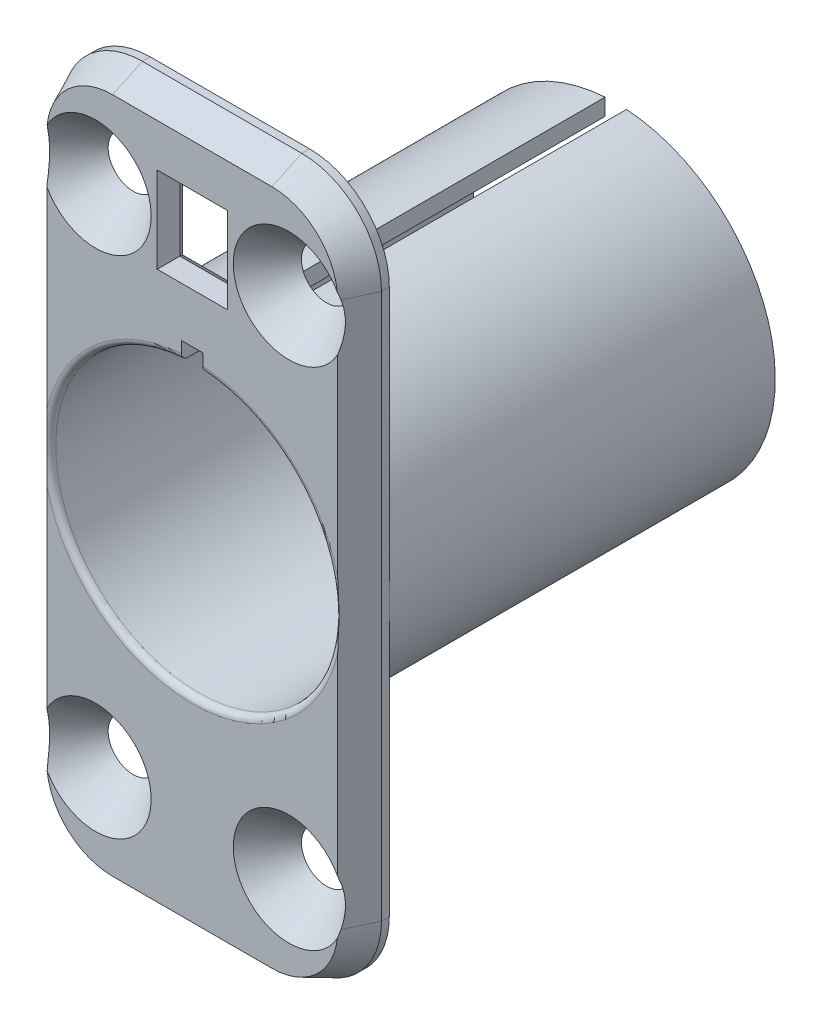
SolidWorks part; units mm, degrees
ref_plane "Front Plane" through (0, 0, 0) normal (0, 0, 1) x (1, 0, 0)
ref_plane "Top Plane" through (0, 0, 0) normal (0, 1, 0) x (1, 0, 0)
ref_plane "Right Plane" through (0, 0, 0) normal (1, 0, 0) x (0, 0, -1)
sketch "Sketch1" plane through (0, 0, 0) normal (0, 0, 1) x (1, 0, 0)
  line L1 (6.35, 28.075) -> (-6.35, 28.075)
  line L2 (12.7, 21.725) -> (12.7, -21.725)
  line L3 (6.35, -28.075) -> (-6.35, -28.075)
  line L4 (-12.7, 21.725) -> (-12.7, -21.725)
  line L5 (12.7, 28.075) -> (-12.7, -28.075) construction
  line L6 (12.7, -28.075) -> (-12.7, 28.075) construction
  arc A0 (6.35, 28.075) -> (12.7, 21.725) centre (6.35, 21.725) cw
  arc A1 (6.35, -28.075) -> (12.7, -21.725) centre (6.35, -21.725) ccw
  arc A2 (-6.35, -28.075) -> (-12.7, -21.725) centre (-6.35, -21.725) cw
  arc A3 (-12.7, 21.725) -> (-6.35, 28.075) centre (-6.35, 21.725) cw
  point P0 (0, 0)
  dimension "D3" = 6.35
  dimension "D1" = 25.4
  dimension "D2" = 56.15
extrude "Boss-Extrude1" add sketch "Sketch1" along normal blind 3
sketch "Sketch2" plane through (0, 0, 0) normal (0, 0, -1) x (-1, 0, 0)
  line L2 (-12.7, -21.725) -> (-12.7, 21.725) construction
  line L3 (12.7, 21.725) -> (12.7, -21.725) construction
  line L4 (-6.35, 28.075) -> (6.35, 28.075) construction
  line L5 (6.35, -28.075) -> (-6.35, -28.075) construction
  circle A1 centre (-7.7, -20.125) radius 2
  circle A2 centre (-7.7, 20.125) radius 2
  circle A3 centre (7.7, 20.125) radius 2
  circle A5 centre (7.7, -20.125) radius 2
  dimension "D1" = 5
  dimension "D2" = 4
  dimension "D5" = 4
  dimension "D6" = 4
  dimension "D7" = 7.95
  dimension "D8" = 7.95
  dimension "D9" = 5
  dimension "D10" = 4
  dimension "D12" = 5
  dimension "D13" = 7.95
  dimension "D3" = 7.95
  dimension "D4" = 5
extrude "Cut-Extrude1" cut sketch "Sketch2" against normal through all
chamfer "Chamfer1" distance 2.38 angle 25 8 edges at (-10.8401, 26.2151, 3) (0, 28.075, 3) (10.8401, 26.2151, 3) (12.7, 0, 3) (10.8401, -26.2151, 3) (0, -28.075, 3) (-10.8401, -26.2151, 3) (-12.7, 0, 3) first distance on face at (-10.1826, 25.5576, 1.5) first distance on face at (0, 28.075, 1.5) first distance on face at (10.1826, 25.5576, 1.5) first distance on face at (12.7, 0, 1.5) first distance on face at (10.1826, -25.5576, 1.5) first distance on face at (0, -28.075, 1.5) first distance on face at (-10.1826, -25.5576, 1.5) first distance on face at (-12.7, 0, 1.5)
sketch "Sketch3" plane through (0, 0, 0) normal (0, 0, -1) x (-1, 0, 0)
  circle A2 centre (0, 0) radius 12.7
  circle A3 centre (0, 0) radius 11.375
  dimension "D1" = 22.75
  dimension "D2" = 25.4
extrude "Boss-Extrude2" add sketch "Sketch3" along normal blind 30.75
sketch "Sketch5" plane through (0, 0, 3) normal (0, 0, 1) x (1, 0, 0)
  line L0 (-11.5902, 21.725) -> (-11.5902, -21.725) construction
  line L6 (11.5902, -21.725) -> (11.5902, 21.725) construction
  line L7 (-2.7902, 16.7) -> (2.7898, 16.7)
  line L8 (-2.7902, 16.7) -> (-2.7902, 23.55)
  line L9 (-2.7902, 23.55) -> (2.7898, 23.55)
  line L10 (2.7898, 16.7) -> (2.7898, 23.55)
  line L11 (-2.7902, 16.7) -> (2.7898, 23.55) construction
  line L12 (-2.7902, 23.55) -> (2.7898, 16.7) construction
  point P4 (-0.0002, 20.125)
  dimension "D1" = 5.58
  dimension "D2" = 6.85
  dimension "D4" = 8.8
  dimension "D5" = 8.8004
extrude "Cut-Extrude3" cut sketch "Sketch5" against normal blind 10
chamfer "Chamfer3" distance 1 angle 50 4 edges at (-0.0002, 16.7, 0) (2.7898, 20.125, 0) (-0.0002, 23.55, 0) (-2.7902, 20.125, 0) first distance on face at (-0.0002, 20.125, 0)
sketch "Sketch6" plane through (0, 0, 0) normal (0, 0, -1) x (-1, 0, 0)
  circle A0 centre (0, 0) radius 11.375
  dimension "D1" = 22.75
extrude "Cut-Extrude4" cut sketch "Sketch6" against normal blind 5
chamfer "Chamfer4" distance 3 angle 39 4 edges at (5.7, -20.125, 3) (-9.7, -20.125, 3) (5.7, 20.125, 3) (-9.7, 20.125, 3) first distance on face at (5.7, -20.125, 3) first distance on face at (-9.7, -20.125, 3) first distance on face at (5.7, 20.125, 3) first distance on face at (-9.7, 20.125, 3)
fillet "Fillet1" radius 0.5 1 edges at (-11.375, 0, 3)
sketch "Sketch7" plane through (0, 0, -30.75) normal (0, 0, -1) x (-1, 0, 0)
  line L2 (-0.85, 11.3432) -> (-0.85, 12.75)
  line L3 (-0.85, 12.75) -> (0.85, 12.75)
  line L4 (0.85, 11.3432) -> (0.85, 12.75)
  line L5 (0, 11.375) -> (0.85, 12.75) construction
  line L6 (-0.85, 12.75) -> (0, 11.375) construction
  arc A0 (0.85, 11.3432) -> (-0.85, 11.3432) centre (0, 0) ccw
  point P3 (0, 11.375)
  dimension "D1" = 1.7
extrude "Cut-Extrude6" cut sketch "Sketch7" against normal blind 35
equation "\"0..005in\"=0.393701"
